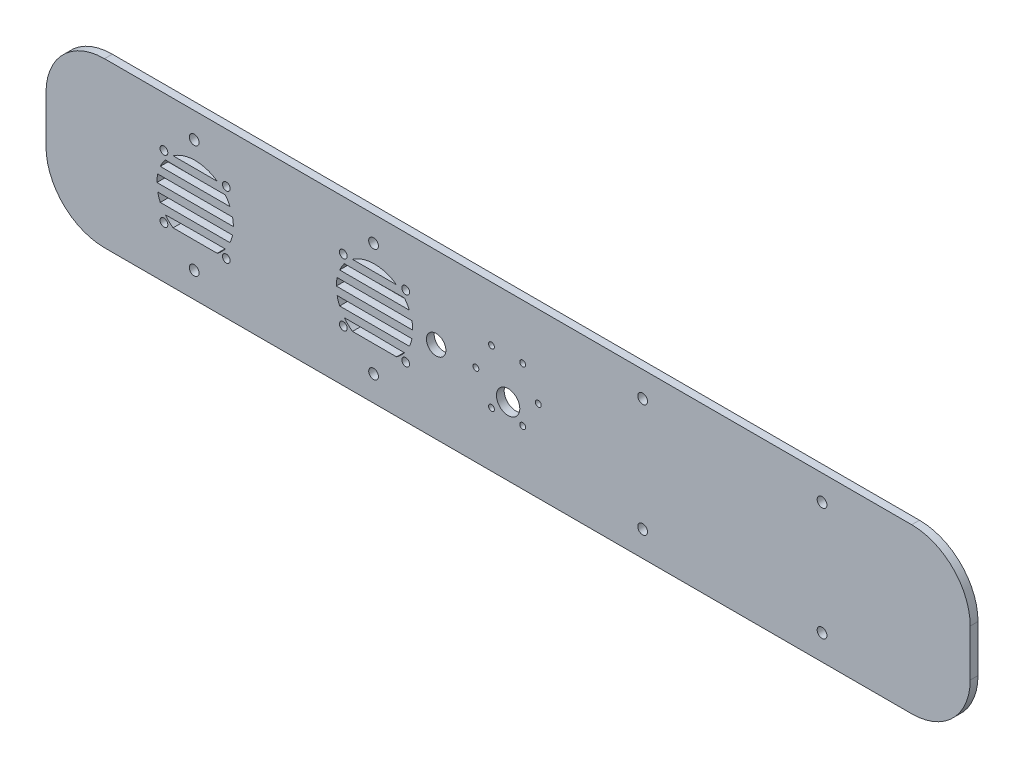
SolidWorks part; units mm, degrees
ref_plane "Alzado" through (0, 0, 0) normal (0, 0, 1) x (1, 0, 0)
ref_plane "Planta" through (0, 0, 0) normal (0, 1, 0) x (1, 0, 0)
ref_plane "Vista lateral" through (0, 0, 0) normal (1, 0, 0) x (0, 0, -1)
sketch "Croquis1" plane through (0, 0, 0) normal (0, 0, 1) x (1, 0, 0)
  line L0 (207, -38) -> (-207, -38)
  line L1 (237, -8) -> (237, 16)
  line L2 (207, 46) -> (-207, 46)
  line L3 (-237, -8) -> (-237, 16)
  line L4 (237, -38) -> (-237, 46) construction
  line L5 (237, 46) -> (-237, -38) construction
  line L6 (0, 4) -> (-24.9, 4) construction
  line L7 (0, 4) -> (15.5, 4) construction
  line L8 (0, 4) -> (0, -3) construction
  arc A0 (-237, 16) -> (-207, 46) centre (-207, 16) cw
  arc A1 (207, -38) -> (237, -8) centre (207, -8) ccw
  arc A2 (207, 46) -> (237, 16) centre (207, 16) cw
  arc A3 (-237, -8) -> (-207, -38) centre (-207, -8) ccw
  circle A22 centre (15.5, 4) radius 1.5
  circle A24 centre (7.4961, -9.8632) radius 1.5
  circle A25 centre (-8.5117, -9.8632) radius 1.5
  circle A26 centre (-16.5156, 4) radius 1.5
  circle A27 centre (-8.5117, 17.8632) radius 1.5
  circle A28 centre (7.4961, 17.8632) radius 1.5
  circle A30 centre (0, -3) radius 6
  point P0 (0, 4)
  dimension "D2" = 30
  dimension "D3" = 30
  dimension "D5" = 15.5
  dimension "D7" = 6
  dimension "D6" = 3
  dimension "D1" = 474
  dimension "D4" = 24.9
  dimension "D8" = 84
  dimension "D10" = 7
extrude "Saliente-Extruir1" add sketch "Croquis1" along normal blind 4
sketch "Croquis3" plane through (0, 0, 4) normal (0, 0, 1) x (1, 0, 0)
  line L0 (-176.5101, 22.4584) -> (-176.5101, 20.4584) construction
  line L1 (207, 46) -> (-207, 46) construction
  line L2 (-207, 46) -> (-177, 46) construction
  line L3 (-144.5101, 20.4584) -> (-142.5101, 20.4584) construction
  line L6 (-171.8135, -11.5416) -> (-149.2066, -11.5416)
  line L13 (-160.5101, 8.4584) -> (-141.3328, 8.4584)
  line L14 (-180.1001, 4.4584) -> (-140.9201, 4.4584)
  line L21 (-160.5101, 8.4584) -> (-179.6874, 8.4584)
  line L22 (-160.5101, 12.4584) -> (-142.628, 12.4584)
  line L23 (-160.5101, 12.4584) -> (-178.3921, 12.4584)
  line L24 (-160.5101, 16.4584) -> (-145.0256, 16.4584)
  line L25 (-160.5101, 16.4584) -> (-175.8506, 16.6419)
  line L26 (-160.5101, 0.4584) -> (-141.3328, 0.4584)
  line L27 (-160.5101, 0.4584) -> (-179.6874, 0.4584)
  line L28 (-160.5101, -3.5416) -> (-142.628, -3.5416)
  line L29 (-160.5101, -3.5416) -> (-178.3921, -3.5416)
  line L30 (-160.5101, -7.5416) -> (-145.0256, -7.5416)
  line L31 (-160.5101, -7.5416) -> (-175.8506, -7.7251)
  line L32 (-171.8135, 20.4584) -> (-149.2066, 20.4584)
  line L37 (-57.2066, 20.4584) -> (-79.8135, 20.4584)
  line L38 (-68.5101, -7.5416) -> (-53.1696, -7.7251)
  line L39 (-68.5101, -7.5416) -> (-83.9945, -7.5416)
  line L40 (-68.5101, -3.5416) -> (-50.628, -3.5416)
  line L41 (-68.5101, -3.5416) -> (-86.3921, -3.5416)
  line L42 (-68.5101, 0.4584) -> (-49.3328, 0.4584)
  line L43 (-68.5101, 0.4584) -> (-87.6874, 0.4584)
  line L44 (-68.5101, 16.4584) -> (-53.1696, 16.6419)
  line L45 (-68.5101, 16.4584) -> (-83.9945, 16.4584)
  line L46 (-68.5101, 12.4584) -> (-50.628, 12.4584)
  line L47 (-68.5101, 12.4584) -> (-86.3921, 12.4584)
  line L48 (-68.5101, 8.4584) -> (-49.3328, 8.4584)
  line L49 (-48.9201, 4.4584) -> (-88.1001, 4.4584)
  line L50 (-68.5101, 8.4584) -> (-87.6874, 8.4584)
  line L51 (-57.2066, -11.5416) -> (-79.8135, -11.5416)
  line L52 (-86.5101, 20.4584) -> (-84.5101, 20.4584) construction
  circle A0 centre (-176.5101, 20.4584) radius 2
  circle A1 centre (-144.5101, 20.4584) radius 2
  circle A2 centre (-176.5101, -11.5416) radius 2
  circle A3 centre (-144.5101, -11.5416) radius 2
  arc A9 (-175.8506, 16.6419) -> (-178.3921, 12.4584) centre (-160.5101, 4.4584) ccw
  arc A10 (-149.2066, 20.4584) -> (-171.8135, 20.4584) centre (-160.5101, 4.4584) ccw
  arc A11 (-142.628, 12.4584) -> (-145.0256, 16.4584) centre (-160.5101, 4.4584) ccw
  arc A12 (-179.6874, 8.4584) -> (-180.1001, 4.4584) centre (-160.5101, 4.4584) ccw
  arc A13 (-179.6874, 0.4584) -> (-178.3921, -3.5416) centre (-160.5101, 4.4584) ccw
  arc A14 (-140.9201, 4.4584) -> (-141.3328, 8.4584) centre (-160.5101, 4.4584) ccw
  arc A15 (-142.628, -3.5416) -> (-141.3328, 0.4584) centre (-160.5101, 4.4584) ccw
  arc A16 (-175.8506, -7.7251) -> (-171.8135, -11.5416) centre (-160.5101, 4.4584) ccw
  arc A17 (-149.2066, -11.5416) -> (-145.0256, -7.5416) centre (-160.5101, 4.4584) ccw
  arc A18 (-79.8135, -11.5416) -> (-83.9945, -7.5416) centre (-68.5101, 4.4584) cw
  arc A19 (-53.1696, -7.7251) -> (-57.2066, -11.5416) centre (-68.5101, 4.4584) cw
  arc A20 (-86.3921, -3.5416) -> (-87.6874, 0.4584) centre (-68.5101, 4.4584) cw
  arc A21 (-88.1001, 4.4584) -> (-87.6874, 8.4584) centre (-68.5101, 4.4584) cw
  arc A22 (-49.3328, 0.4584) -> (-50.628, -3.5416) centre (-68.5101, 4.4584) cw
  arc A23 (-49.3328, 8.4584) -> (-48.9201, 4.4584) centre (-68.5101, 4.4584) cw
  arc A24 (-86.3921, 12.4584) -> (-83.9945, 16.4584) centre (-68.5101, 4.4584) cw
  arc A25 (-79.8135, 20.4584) -> (-57.2066, 20.4584) centre (-68.5101, 4.4584) cw
  arc A26 (-53.1696, 16.6419) -> (-50.628, 12.4584) centre (-68.5101, 4.4584) cw
  circle A27 centre (-84.5101, -11.5416) radius 2
  circle A28 centre (-52.5101, -11.5416) radius 2
  circle A29 centre (-84.5101, 20.4584) radius 2
  circle A30 centre (-52.5101, 20.4584) radius 2
  dimension "D5" = 4
  dimension "D6" = 4
  dimension "D7" = 4
  dimension "D8" = 4
  dimension "D15" = 39.18
  dimension "D2" = 30
  dimension "D3" = 32
  dimension "D4" = 32
  dimension "D14" = 60
  dimension "D17" = 4
  dimension "D18" = 4
  dimension "D19" = 4
extrude "Cortar-Extruir1" cut sketch "Croquis3" against normal blind 10
sketch "Croquis4" plane through (0, 0, 4) normal (0, 0, 1) x (1, 0, 0)
  circle A0 centre (-36.9, 4) radius 5
  dimension "D2" = 10
extrude "Cortar-Extruir2" cut sketch "Croquis4" against normal blind 5
sketch "Croquis5" plane through (0, 0, 0) normal (0, 0, -1) x (-1, 0, 0)
  line L0 (161, 33) -> (161, 46) construction
  line L1 (-207, 46) -> (207, 46) construction
  line L2 (69, -25) -> (69, -38) construction
  line L3 (161, -25) -> (161, -38) construction
  line L4 (-161, -25) -> (-161, -38) construction
  line L7 (69, 33) -> (69, 46) construction
  line L8 (-69, -25) -> (-69, -38) construction
  line L9 (-69, 33) -> (-69, 46) construction
  line L10 (-161, 33) -> (-161, 46) construction
  circle A0 centre (69, 33) radius 2.5
  circle A1 centre (161, 33) radius 2.5
  circle A2 centre (161, -25) radius 2.5
  circle A3 centre (69, -25) radius 2.5
  circle A4 centre (-69, -25) radius 2.5
  circle A5 centre (-161, -25) radius 2.5
  circle A6 centre (-161, 33) radius 2.5
  circle A7 centre (-69, 33) radius 2.5
  dimension "D2" = 5
  dimension "D4" = 5
  dimension "D1" = 13
  dimension "D3" = 13
extrude "Cortar-Extruir3" cut sketch "Croquis5" against normal blind 10
